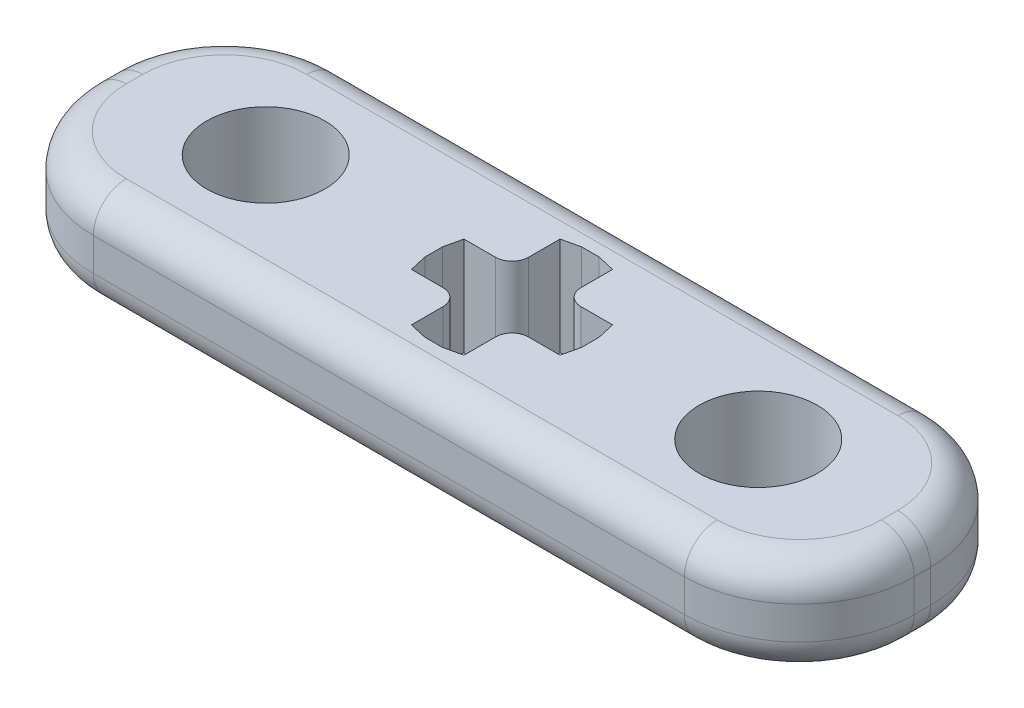
SolidWorks part; units mm, degrees
ref_plane "Front Plane" through (0, 0, 0) normal (0, 0, 1) x (1, 0, 0)
ref_plane "Top Plane" through (0, 0, 0) normal (0, 1, 0) x (1, 0, 0)
ref_plane "Right Plane" through (0, 0, 0) normal (1, 0, 0) x (0, 0, -1)
sketch "Sketch1" plane through (0, 0, 0) normal (0, 1, 0) x (1, 0, 0)
  line L0 (-0.8, 0.8) -> (-0.8, 2.2627)
  line L1 (-12.5, -3.75) -> (12.5, -3.75)
  line L2 (-12.5, -3.75) -> (-12.5, 3.75)
  line L3 (-12.5, 3.75) -> (12.5, 3.75)
  line L4 (12.5, -3.75) -> (12.5, 3.75)
  line L5 (-12.5, -3.75) -> (12.5, 3.75) construction
  line L6 (-12.5, 3.75) -> (12.5, -3.75) construction
  line L8 (-5, -3.75) -> (-5, 3.75)
  line L10 (5, -3.75) -> (5, 3.75)
  line L11 (3.5787, -3.75) -> (6.4358, 3.75) construction
  line L12 (3.5642, 3.75) -> (6.4213, -3.75) construction
  line L13 (-0.8, 2.2627) -> (-0.2701, 2.3847)
  line L14 (-0.2701, 2.3847) -> (0.2701, 2.3847)
  line L15 (0.2701, 2.3847) -> (0.8, 2.2627)
  line L16 (0.8, 2.2627) -> (0.8, 0.8)
  line L17 (0.8, 0.8) -> (2.2627, 0.8)
  line L18 (2.2627, 0.8) -> (2.3847, 0.2701)
  line L19 (2.3847, 0.2701) -> (2.3847, -0.2701)
  line L20 (2.3847, -0.2701) -> (2.2627, -0.8)
  line L21 (2.2627, -0.8) -> (0.8, -0.8)
  line L22 (0.8, -0.8) -> (0.8, -2.2627)
  line L23 (0.8, -2.2627) -> (0.2701, -2.3847)
  line L24 (0.2701, -2.3847) -> (-0.2701, -2.3847)
  line L25 (-0.2701, -2.3847) -> (-0.8, -2.2627)
  line L26 (-0.8, -2.2627) -> (-0.8, -0.8)
  line L27 (-0.8, -0.8) -> (-2.2627, -0.8)
  line L28 (-2.2627, -0.8) -> (-2.3847, -0.2701)
  line L29 (-2.3847, -0.2701) -> (-2.3847, 0.2701)
  line L30 (-2.3847, 0.2701) -> (-2.2627, 0.8)
  line L31 (-2.2627, 0.8) -> (-0.8, 0.8)
  line L32 (-5, 3.75) -> (5, 3.75) construction
  circle A1 centre (0, 0) radius 3
  point P2 (0, 3.75)
  dimension "D1" = 6
  dimension "D3" = 10
  dimension "D4" = 25
  dimension "D5" = 7.5
extrude "Boss-Extrude1" add sketch "Sketch1" along normal blind 3 contours L1 L10 L3 L8 | L3 L10 L8 | L1 L8 L3 L2 | L10 L1 L8 | L2 L1 L4 L3 | L0 L13 L14 L15 L16 L17 L18 L19 L20 L21 L22 L23 L24 L25 L26 L27 L28 L29 L30 L31 region at (-8.75, 0, 0) region at (-4.875, 0, 0)
fillet "Fillet4" radius 3.5 4 edges at (12.5, 1.5, -3.75) (12.5, 1.5, 3.75) (-12.5, 1.5, 3.75) (-12.5, 1.5, -3.75)
hole_wizard "M3 Clearance Hole1" positions "Sketch2" profile "Sketch3" hole size "M3" standard "ANSI Metric" end condition through all
sketch "Sketch2" plane through (0, 0, 0) normal (0, 1, 0) x (1, 0, 0)
  line L0 (-7.5, 0) -> (7.5, 0)
  line L2 (12.5, -0.25) -> (12.5, 0.25) construction
  point P0 (-7.5, 0)
  point P2 (7.5, 0)
  point P26 (0, 0)
  dimension "D1" = 5
sketch "Sketch3" plane through (-7.5, 0, 0) normal (1, 0, 0) x (0, 0, -1)
  line L0 (0, 0) -> (0, 3)
  line L1 (0, 3) -> (1.8, 3)
  line L2 (1.8, 3) -> (1.8, 0)
  line L5 (1.8, 0) -> (0, 0)
  line L11 (0, -6.35) -> (0, 107.95) construction
  dimension "Thru Hole Dia." = 3.6
  dimension "Thru Hole Depth" = 3
fillet "Fillet6" radius 1 16 edges at (-11.4749, 3, 2.7249) (0, 3, 3.75) (11.4749, 3, 2.7249) (11.4749, 3, -2.7249) (0, 3, -3.75) (-11.4749, 3, -2.7249) (-11.4749, 0, 2.7249) (0, 0, 3.75) (11.4749, 0, 2.7249) (11.4749, 0, -2.7249) (0, 0, -3.75) (-11.4749, 0, -2.7249) (12.5, 3, 0) (12.5, 0, 0) (-12.5, 3, 0) (-12.5, 0, 0)
fillet "Fillet7" radius 0.5 4 edges at (0.8, 1.5, 0.8) (-0.8, 1.5, 0.8) (0.8, 1.5, -0.8) (-0.8, 1.5, -0.8)
